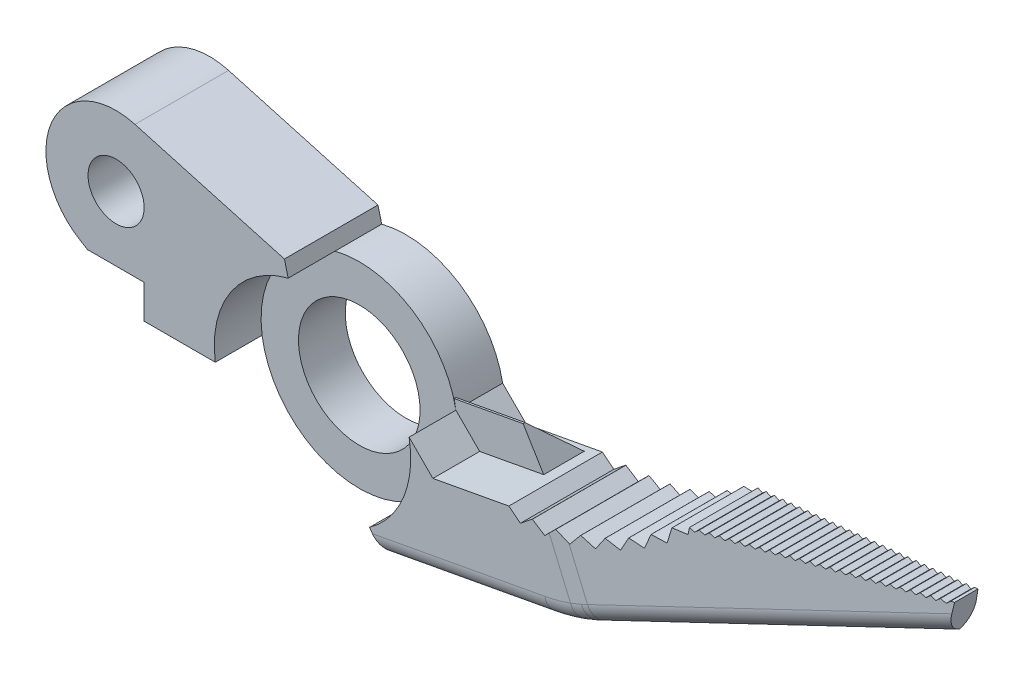
SolidWorks part; units mm, degrees
ref_plane "Front Plane" through (0, 0, 0) normal (0, 0, 1) x (1, 0, 0)
ref_plane "Top Plane" through (0, 0, 0) normal (0, 1, 0) x (1, 0, 0)
ref_plane "Right Plane" through (0, 0, 0) normal (1, 0, 0) x (0, 0, -1)
sketch "Sketch1" plane through (0, 0, 0) normal (0, 0, 1) x (1, 0, 0)
  line L0 (0, 0) -> (38.4509, 0) construction
  line L1 (0, 0) -> (32.4474, 6.0138) construction
  line L2 (-9.4882, 8.1109) -> (1.4165, 5.0553)
  line L3 (-12.417, 1.277) -> (-2.6838, -4.5122)
  line L4 (0, 0) -> (32.4474, 6.0138)
  line L5 (32.4474, 6.0138) -> (32.0857, 4.2505)
  line L6 (32.0857, 4.2505) -> (13.677, -3.5673)
  line L7 (13.677, -3.5673) -> (3.8444, -5.3897)
  line L8 (3.8444, -5.3897) -> (0, 0)
  circle A0 centre (0, 0) radius 5.25
  circle A1 centre (-10.5, 4.5) radius 3.75
  dimension "D1" = 10.5
  dimension "D2" = 7.5
  dimension "D3" = 10.5
  dimension "D4" = 4.5
  dimension "D5" = 33
  dimension "D6" = 10.5
  dimension "D7" = 65
  dimension "D8" = 10
  dimension "D9" = 6
  dimension "D10" = 20
  dimension "D11" = 1.8
extrude "Boss-Extrude1" add sketch "Sketch1" along normal mid plane 5 contours A1 | A1 L3 A0 L2 | L4 A0 L8 | L8 A0 L4 | A0 L8 L7 L6 L5 L4 region at (-5.8996, 2.5284, 0) region at (-10.5, 4.5, 0) region at (-0.6773, 0.2736, 0) region at (3.0739, -1.2419, 0) region at (15.8799, 0.3406, 0)
sketch "Sketch2" plane through (0, 0, 2.5) normal (0, 0, 1) x (1, 0, 0)
  line L0 (-12.0263, 1.0446) -> (-9, 1.0446)
  line L1 (-12.417, 1.277) -> (-2.6838, -4.5122) construction
  line L2 (-9, 1.0446) -> (-9, -0.7554)
  line L3 (-9, -0.7554) -> (-5.1954, -0.7554)
  line L4 (-12.0263, 1.0446) -> (-2.6838, -4.5122)
  arc A0 (-5.1954, -0.7554) -> (-2.6838, -4.5122) centre (0, 0) ccw
  point P6 (-18.6598, 7.6557)
  line M13 (-12.417, 1.277) -> (-2.6838, -4.5122)
  dimension "D2" = 10.5
  dimension "D1" = 1.8
  dimension "D3" = 9
extrude "Cut-Extrude1" cut sketch "Sketch2" against normal through all and the other way through all contours L2 L0 M13 | A0 L3 M13 region at (-6.0482, -1.8017, 2.5) region at (-10.0088, 0.4446, 2.5)
sketch "Sketch3" plane through (3.3732, -7.9431, 0) normal (0.3909, -0.9204, 0) x (0.9204, 0.3909, 0)
  line L0 (0, 0) -> (32.2165, 0) construction
  line L1 (32.2165, 2.5) -> (32.2165, -2.5) construction
  line L2 (12.2165, 2.5) -> (32.2165, 2.5)
  line L3 (31.1944, 2.5) -> (11.1944, 2.5) construction
  line L4 (32.2165, 2.5) -> (32.2165, 0.625)
  line L5 (32.2165, 0.625) -> (12.2165, 2.5)
  line L6 (32.2165, -2.5) -> (32.2165, -0.625)
  line L7 (12.2165, -2.5) -> (32.2165, -2.5)
  line L8 (32.2165, -0.625) -> (12.2165, -2.5)
  dimension "D1" = 1.25
  dimension "D2" = 20
extrude "Cut-Extrude2" cut sketch "Sketch3" against normal through all
fillet "Fillet1" radius 10 3 edges at (13.4609, -0.4437, -2.5) (13.4609, -0.4437, 2.5) (13.677, -3.5673, 0)
fillet "Fillet2" radius 1 10 edges at (8.2218, -4.5784, 2.5) (13.3992, -3.5845, 2.5) (14.8663, -3.0622, 2.4728) (23.5661, 0.6324, 1.5886) (8.2218, -4.5784, -2.5) (13.3992, -3.5845, -2.5) (14.8663, -3.0622, -2.4728) (23.5661, 0.6324, -1.5886)
sketch "Sketch4" plane through (0, 0, 2.5) normal (0, 0, 1) x (1, 0, 0)
  line L0 (5.1621, 0.9567) -> (6.4349, -0.3161)
  line L1 (6.4349, -0.3161) -> (10.4957, 0.4366)
  line L2 (32.4474, 6.0138) -> (12.7731, 2.3674) construction
  line L4 (5.1621, 0.9567) -> (11.833, 2.1931) construction
  line L6 (5.1621, 0.9567) -> (19, 3.5214)
  arc A0 (10.4957, 0.4366) -> (19, 3.5214) centre (10.9577, 12.4277) ccw
  dimension "D4" = 12
  dimension "D1" = 1.8
  dimension "D2" = 1.4834
  dimension "D3" = 4.13
  dimension "D5" = 19
extrude "Cut-Extrude3" cut sketch "Sketch4" against normal through all
sketch "Sketch6" plane through (0, 0, 0) normal (0, 0, 1) x (1, 0, 0)
  line L0 (32.2508, 5.9773) -> (32.0323, 5.7843)
  line L1 (32.4474, 6.0138) -> (19, 3.5214) construction
  line L2 (32.0323, 5.7843) -> (31.7591, 5.8862)
  line L3 (31.7591, 5.8862) -> (32.2508, 5.9773)
  line L4 (32.0323, 5.7843) -> (32.0049, 5.9318) construction
  point P4 (0, 0)
  point P8 (29.8103, 5.6777)
  dimension "D1" = 0.5
  dimension "D2" = 0.15
  dimension "D3" = 0.2
extrude "Cut-Extrude4" cut sketch "Sketch6" against normal mid plane 5
pattern_linear "LPattern1" count 28 spacing 0.5 along (-0.9833, -0.1822, 0) of "Cut-Extrude4"
sketch "Sketch7" plane through (0, 0, 2.5) normal (0, 0, 1) x (1, 0, 0)
  circle A0 centre (0, 0) radius 5.25
  dimension "D1" = 10.5
extrude "Cut-Extrude5" cut sketch "Sketch7" against normal blind 2.5
sketch "Sketch8" plane through (0, 0, 2.5) normal (0, 0, 1) x (1, 0, 0)
  line L0 (10.4957, 0.4366) -> (11.7457, 0.4536)
  line L1 (11.7457, 0.4536) -> (11.1101, -0.0551)
  line L2 (11.1101, -0.0551) -> (10.4957, 0.4366)
  line L3 (11.1101, -0.0551) -> (11.1101, 0.4449) construction
  arc A0 (10.4957, 0.4366) -> (12.5383, 0.5322) centre (10.9577, 12.4277) ccw construction
  dimension "D1" = 1.25
  dimension "D2" = 0.5
extrude "Cut-Extrude6" cut sketch "Sketch8" against normal through all
pattern_circular "CirPattern1" count 8 every 6 about axis through (10.9577, 12.4277, -2.5244) along (0, 0, 1) of "Cut-Extrude6"
ref_plane "Plane1" through (5.1621, 0.9567, 0) normal (0.9833, 0.1822, 0) x (0, 0, -1)
sketch "Sketch9" plane through (5.1621, 0.9567, 0) normal (0.9833, 0.1822, 0) x (0, 0, -1)
  line L0 (0.1, 0.5) -> (0, 0.5)
  line L1 (0, 3.5184) -> (0, -3.9475) construction
  line L2 (0, 0.5) -> (0, -1.8)
  line L3 (0, 5.25) -> (0, -5.25) construction
  line L4 (0, -1.8) -> (2.5, -1.8)
  line L5 (2.5, -2.0456) -> (2.5, -4.8877) construction
  line L6 (2.5, -1.8) -> (0.1, 0.5)
  dimension "D1" = 0.1
  dimension "D2" = 0.5
  dimension "D3" = 2.3
extrude "Boss-Extrude2" add sketch "Sketch9" along normal blind 4.5
sketch "Sketch10" plane through (0, 0, 0) normal (0, 0, 1) x (1, 0, 0)
  line L0 (8.7582, 2.1317) -> (9.4956, 2.2684)
  line L1 (9.4956, 2.2684) -> (5.071, 1.4484) construction
  line L2 (9.4956, 2.2684) -> (9.8571, 0.3182)
  line L3 (9.8571, 0.3182) -> (8.7582, 2.1317)
  dimension "D1" = 0.75
extrude "Cut-Extrude7" cut sketch "Sketch10" against normal blind 4.5
sketch "Sketch11" plane through (0, 0, 2.5) normal (0, 0, 1) x (1, 0, 0)
  circle A0 centre (-10.5, 4.5) radius 1.5
  dimension "D1" = 3
extrude "Cut-Extrude8" cut sketch "Sketch11" against normal through all
sketch "Sketch12" plane through (0, -0.7554, 0) normal (0, -1, 0) x (1, 0, 0)
  line L0 (-9, -2.5) -> (-5.1954, 2.5) construction
  circle A0 centre (-7.0977, 0) radius 1.25
  dimension "D1" = 2.5
extrude "Cut-Extrude9" cut sketch "Sketch12" against normal blind 2
sketch "Sketch13" plane through (0, 0, 2.5) normal (0, 0, 1) x (1, 0, 0)
  line L0 (0, 0) -> (1.4165, 5.0553)
  line L1 (1.4165, 5.0553) -> (-1.5021, 5.8731)
  line L2 (-9.4882, 8.1109) -> (1.4165, 5.0553) construction
  line L3 (-1.5021, 5.8731) -> (0, 0)
  arc A0 (1.4165, 5.0553) -> (-5.1954, -0.7554) centre (0, 0) ccw construction
  arc A1 (1.4165, 5.0553) -> (-5.1954, -0.7554) centre (0, 0) ccw
  arc M4 (-5.1954, -0.7554) -> (1.4165, 5.0553) centre (0, 0) cw
  line M5 (1.4165, 5.0553) -> (-9.4882, 8.1109)
  dimension "D1" = 30
extrude "Cut-Extrude10" cut sketch "Sketch13" against normal through all contours L3 M5 M4 region at (-0.6908, 5.4242, 2.5)
sketch "Sketch14" plane through (0, 0, 0) normal (0, 0, 1) x (1, 0, 0)
  circle A0 centre (0, 0) radius 3.25
  dimension "D1" = 6.5
extrude "Cut-Extrude11" cut sketch "Sketch14" against normal through all
